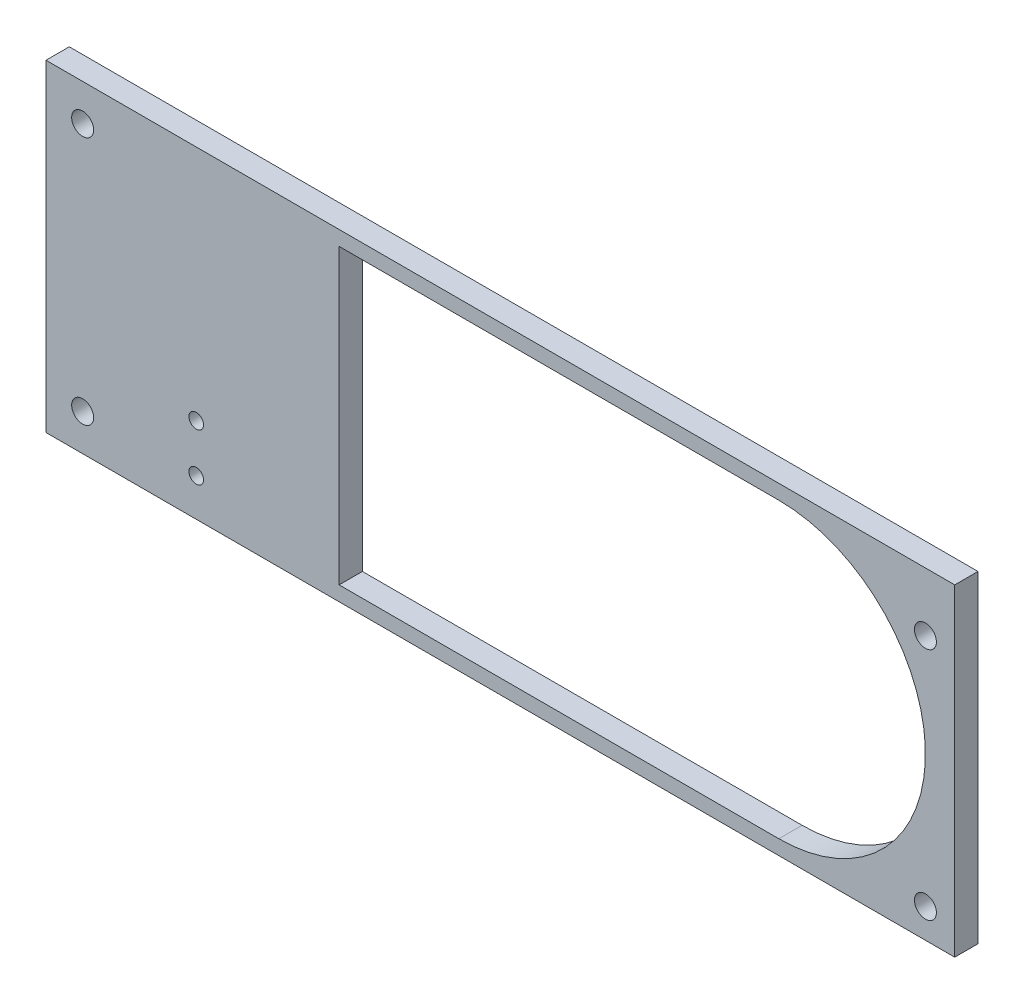
SolidWorks part; units mm, degrees
material "Acrylic (Medium-high impact)"
ref_plane "Front Plane" through (0, 0, 0) normal (0, 0, 1) x (1, 0, 0)
ref_plane "Top Plane" through (0, 0, 0) normal (0, 1, 0) x (1, 0, 0)
ref_plane "Right Plane" through (0, 0, 0) normal (1, 0, 0) x (0, 0, -1)
sketch "Sketch1" plane through (0, 0, 0) normal (0, 0, 1) x (1, 0, 0)
  line L3 (0, 0) -> (100, 0)
  line L4 (0, 0) -> (0, 44)
  line L5 (0, 44) -> (100, 44)
  line L6 (40, 2) -> (40, 42)
  line L7 (40, 42) -> (100, 42)
  line L8 (40, 2) -> (100, 2)
  line L9 (100, 44) -> (124, 44)
  line L10 (124, 44) -> (124, 0)
  line L11 (124, 0) -> (100, 0)
  arc A2 (100, 2) -> (100, 42) centre (100, 22) ccw
  circle A3 centre (120, 36) radius 1.5
  circle A4 centre (120, 4) radius 1.5
  circle A5 centre (5, 39) radius 1.5
  circle A6 centre (5, 5) radius 1.5
  circle A7 centre (20.5, 11.65) radius 1
  circle A8 centre (20.5, 5.15) radius 1
  point P13 (120, 22)
  point P25 (0, 0)
  dimension "D1" = 20
  dimension "D7" = 3
  dimension "D8" = 3
  dimension "D9" = 3
  dimension "D10" = 3
  dimension "D17" = 2
  dimension "D18" = 2
  dimension "D2" = 2
  dimension "D3" = 2
  dimension "D4" = 40
  dimension "D5" = 120
  dimension "D6" = 124
  dimension "D11" = 8
  dimension "D12" = 4
  dimension "D13" = 4
  dimension "D14" = 5
  dimension "D15" = 5
  dimension "D16" = 5
  dimension "D19" = 20.5
  dimension "D20" = 5.15
  dimension "D21" = 6.5
extrude "Boss-Extrude1" add sketch "Sketch1" along normal blind 3.175
